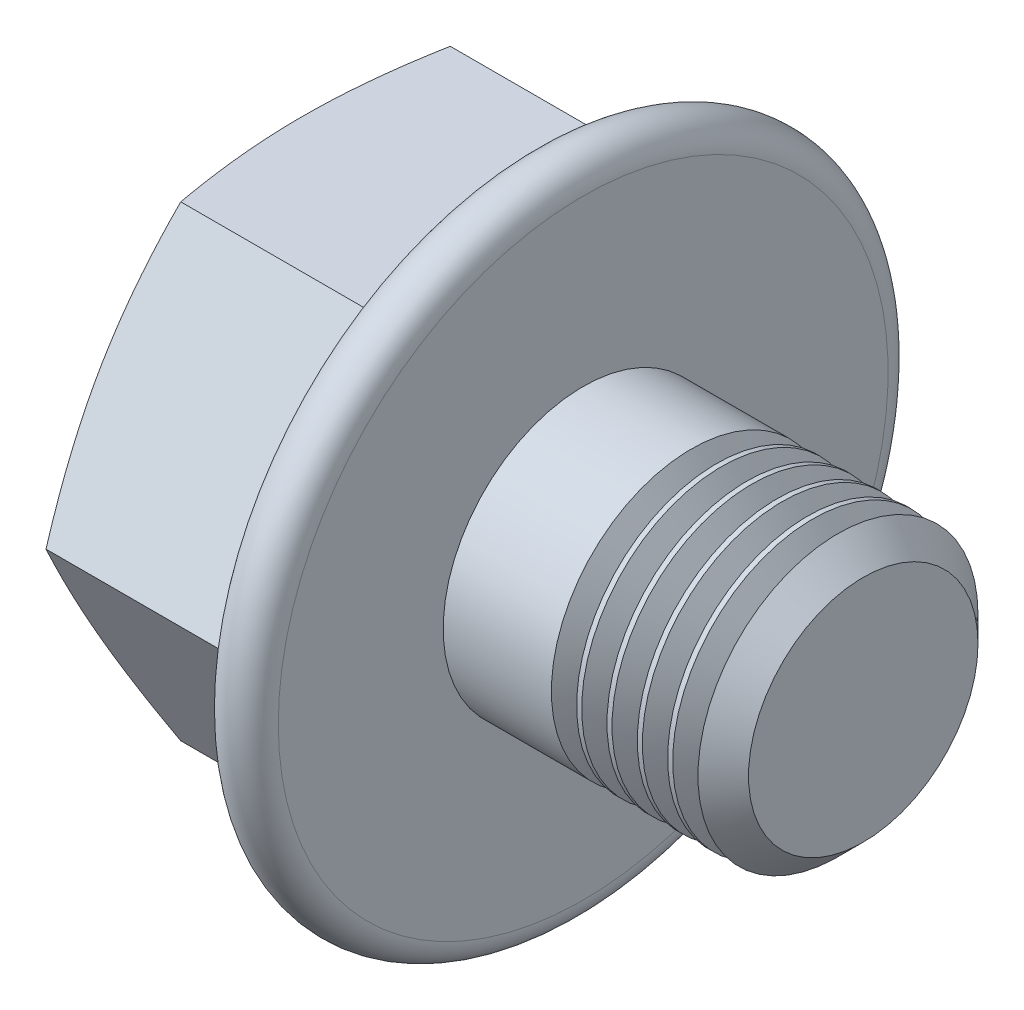
SolidWorks part; units mm, degrees
ref_plane "Front" through (0, 0, 0) normal (0, 0, 1) x (1, 0, 0)
ref_plane "Top" through (0, 0, 0) normal (0, 1, 0) x (1, 0, 0)
ref_plane "Right" through (0, 0, 0) normal (1, 0, 0) x (0, 0, -1)
sketch "Sketch1" plane through (0, 0, 0) normal (1, 0, 0) x (0, 0, -1)
  line L1 (5.7735, 0) -> (2.8868, 5)
  line L2 (2.8868, 5) -> (-2.8868, 5)
  line L3 (-2.8868, 5) -> (-5.7735, 0)
  line L4 (-5.7735, 0) -> (-2.8868, -5)
  line L5 (-2.8868, -5) -> (2.8868, -5)
  line L6 (2.8868, -5) -> (5.7735, 0)
  circle A0 centre (0, 0) radius 5 construction
  dimension "s" = 10
extrude "BaseHead" add sketch "Sketch1" along normal blind 6.6
ref_plane "Plane1" through (9.6, 0, 0) normal (1, 0, 0) x (0, 0, -1)
sketch "Sketch2" plane through (6.6, 0, 0) normal (1, 0, 0) x (0, 0, -1)
  circle A0 centre (0, 0) radius 3
  dimension "d" = 6
extrude "BaseBody" add sketch "Sketch2" along normal blind 6
cosmetic thread "ThreadCosmetic1" [suppressed] parameters "b"=3, "D2"=4.917
sketch "Sketch3" plane through (-0.4952, 0, 6.2687) normal (0, 1, 0) x (0, 0, -1)
  line L0 (12.0422, -0.4952) -> (12.0422, -1.3591)
  line L2 (12.0422, -1.3591) -> (9.6687, -0.4952)
  line L4 (9.6687, -0.4952) -> (12.0422, -0.4952)
  line L5 (6.2687, 4.1693) -> (6.2687, -11.9236) construction
  dimension "D1" = 20
  dimension "da" = 6.8
revolve "HeadChamfer" cut sketch "Sketch3" angle 360 about L5
sketch "Sketch5" plane through (-0.1752, 0, 7.2752) normal (0, 1, 0) x (0, 0, -1)
  line L0 (7.2752, -6.7752) -> (7.2752, -7.1738) construction
  line L2 (7.2752, -6.7752) -> (13.8081, -6.7752)
  line L3 (14.002, -5.6752) -> (7.2752, -3.2268)
  line L4 (7.2752, -3.2268) -> (7.2752, -6.7752)
  line L7 (7.2752, 4.4893) -> (7.2752, -11.6035) construction
  arc A0 (13.8081, -6.7752) -> (14.002, -5.6752) centre (13.8081, -6.2081) ccw
  dimension "D3" = 20
  dimension "c" = 1.1
  dimension "dc" = 14.2
revolve "Flange" add sketch "Sketch5" angle 360 about L0
fillet "HeadFillet" [suppressed] radius 0.4
fillet "FlangeHexFillet" radius 0.4 6 edges
chamfer "Chamfer1" distance 0.5415 angle 45 1 edges at (12.6, 0, -3)
sketch "Sketch6" plane through (0, 0, 0) normal (0, 0, 1) x (1, 0, 0)
  line L0 (11.517, 3.5415) -> (12.0585, 3.5415)
  line L1 (12.0585, 3.5415) -> (12.0585, 3)
  line L2 (12.0585, 3) -> (11.7877, 2.531)
  line L3 (11.7877, 2.531) -> (11.517, 3)
  line L4 (11.517, 3) -> (11.517, 3.5415)
  line L5 (12.0585, 3) -> (6.6, 3) construction
  dimension "D1" = 0.5415
revolve "Cut-Revolve10" cut sketch "Sketch6" angle 360 about axis through (12.6, 0, 0) along (-1, 0, 0)
pattern_linear "LPattern10" count 5 along (-1, 0, 0) of "Cut-Revolve10"
equation "\"D1@Chamfer1\" = (  \"d@Sketch2\" - \"D2@ThreadCosmetic1\" )  / 2"
equation "\"b@ThreadCosmetic1\" = \"l@BaseBody\" - \"lg@Plane1\""
equation "\"da@Sketch3\" = \"s@Sketch1\""
equation "\"D1@Sketch6\" =  ( \"d@Sketch2\" - \"D2@ThreadCosmetic1\" )  / 2"
equation "\"pitch@LPattern10\" = 1.2 * \"D1@Sketch6\""
equation "\"D1@LPattern10\" = \"b@ThreadCosmetic1\" / \"pitch@LPattern10\""
